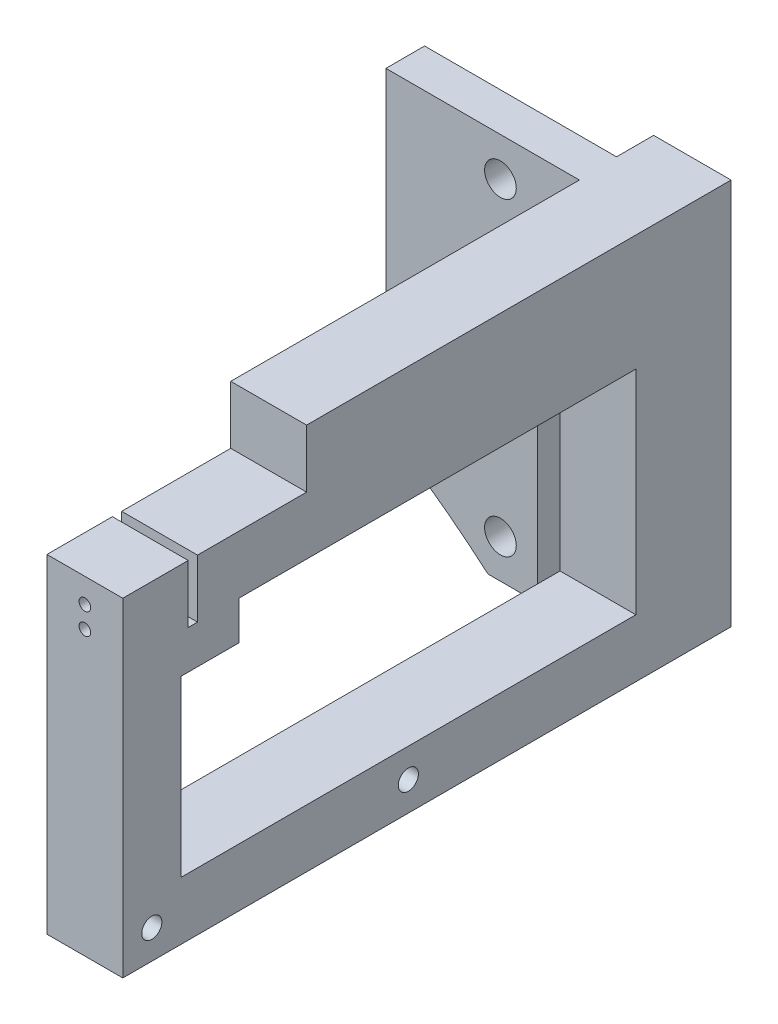
SolidWorks part; units mm, degrees
ref_plane "Front Plane" through (0, 0, 0) normal (0, 0, 1) x (1, 0, 0)
ref_plane "Top Plane" through (0, 0, 0) normal (0, 1, 0) x (1, 0, 0)
ref_plane "Right Plane" through (0, 0, 0) normal (1, 0, 0) x (0, 0, -1)
sketch "Sketch1" plane through (0, 0, 0) normal (0, 0, 1) x (1, 0, 0)
  line L0 (95.25, -31.75) -> (86.8503, -31.75) construction
  line L1 (94.996, -31.75) -> (86.8503, -31.75)
  line L2 (70.104, -19.2524) -> (70.104, -19.41)
  line L32 (70.104, 22.225) -> (70.104, 31.75)
  line L33 (70.104, -19.2524) -> (70.104, 22.225)
  line L34 (70.104, -19.2524) -> (70.104, 22.225)
  line L35 (101.6, 31.75) -> (3.175, 31.75) construction
  line L36 (101.6, 22.479) -> (101.6, 31.75)
  line L54 (70.104, 31.75) -> (101.6, 31.75)
  line L58 (94.996, 22.479) -> (101.6, 22.479)
  line L59 (94.996, -31.75) -> (94.996, 22.479)
  line L60 (94.996, 22.479) -> (101.6, 22.479)
  line L61 (94.996, -31.75) -> (94.996, 22.479)
  circle A0 centre (88.9, -25.4) radius 2.6 construction
  circle A1 centre (88.9, -25.4) radius 2.6
  circle A6 centre (88.9, 25.4) radius 2.6 construction
  circle A7 centre (88.9, 25.4) radius 2.6
  arc A8 (86.8503, -31.75) -> (69.85, -19.2524) centre (0, -132.08) ccw construction
  arc A9 (86.8503, -31.75) -> (70.104, -19.41) centre (0, -132.08) ccw
  dimension "D2" = 0.254
  dimension "D3" = 0.254
extrude "Boss-Extrude1" add sketch "Sketch1" along normal blind 6.35
sketch "Sketch2" plane through (0, 0, 6.35) normal (0, 0, 1) x (1, 0, 0)
  line L0 (101.6, 22.479) -> (101.854, 22.479)
  line L1 (94.996, 22.479) -> (101.6, 22.479) construction
  line L2 (101.854, 22.479) -> (101.854, -31.75)
  line L3 (101.854, -31.75) -> (114.3, -31.75)
  line L4 (114.3, -31.75) -> (114.3, 31.75)
  line L5 (114.3, 31.75) -> (101.6, 31.75)
  line L6 (101.6, 22.479) -> (101.6, 31.75) construction
  line L7 (101.6, 31.75) -> (101.6, 22.479)
  point P7 (0, 0)
  dimension "D1" = 12.7
  dimension "D2" = 0.254
extrude "Boss-Extrude2" add sketch "Sketch2" against normal offset from surface (12.446 mm away) 0.254
sketch "Sketch3" plane through (114.3, 0, 0) normal (1, 0, 0) x (0, 0, -1)
  line L0 (-6.35, -31.75) -> (-6.35, 22.225)
  line L1 (-93.725, -31.75) -> (-93.725, 22.225)
  line L2 (-93.725, 22.225) -> (-87.375, 22.225)
  line L4 (6.35, -31.75) -> (-93.725, -31.75) construction
  line L5 (-87.375, 22.225) -> (0, 22.225) construction
  line L6 (-84.2, 12.7) -> (-84.2, -22.225) construction
  line L7 (-84.2, -22.225) -> (-9.525, -22.225) construction
  line L8 (-9.525, 12.7) -> (-84.2, 12.7) construction
  line L9 (-9.525, -22.225) -> (-9.525, 12.7) construction
  line L10 (-6.35, -31.75) -> (-93.725, -31.75)
  line L11 (-87.375, 22.225) -> (-6.35, 22.225)
  line L12 (-84.2, 12.7) -> (-84.2, -22.225)
  line L13 (-84.2, -22.225) -> (-9.525, -22.225)
  line L14 (-9.525, 12.7) -> (-84.2, 12.7)
  line L15 (-9.525, -22.225) -> (-9.525, 12.7)
  line L16 (-87.375, 22.225) -> (0, 22.225) construction
  line L17 (-6.35, -31.75) -> (-6.35, 31.75) construction
  line L18 (-84.2, -4.7625) -> (-9.525, -4.7625)
extrude "Boss-Extrude4" add sketch "Sketch3" against normal offset from surface (12.446 mm away) 0.254 contours L11 L2 L1 L10 L8 L15 L13 L12 L14 region at (114.3, -30.723, 50.0375)
sketch "Sketch6" plane through (0, 22.225, 0) normal (0, 1, 0) x (1, 0, 0)
  line L1 (101.854, -6.35) -> (114.3, -6.35)
  line L2 (101.854, -6.35) -> (101.854, -63.5625)
  line L3 (101.854, -63.5625) -> (114.3, -63.5625)
  line L4 (114.3, -6.35) -> (114.3, -63.5625)
  line L5 (114.3, -93.725) -> (114.3, -6.35) construction
  line L6 (57.15, -65.15) -> (-95.25, -65.15) construction
  point P5 (107.95, -58.3606)
  dimension "D1" = 1.5875
extrude "Boss-Extrude5" add sketch "Sketch6" along normal up to surface (9.525 mm away) up to face at (95.3347, 31.75, 0.0847)
sketch "Sketch7" plane through (114.3, 0, 0) normal (1, 0, 0) x (0, 0, -1)
  line L1 (-84.2, -22.225) -> (-9.525, -22.225) construction
  line L2 (-93.725, -31.75) -> (-93.725, 22.225) construction
  line L3 (-155.075, -31.75) -> (-45.075, -31.75) construction
  circle A0 centre (-88.9625, -26.9875) radius 1.65
  circle A1 centre (-46.8625, -26.9875) radius 1.65
  point P4 (0, 0)
  point P5 (-50.3003, -43.0881)
  point P8 (0, 0)
  point P9 (-49.9562, -28.12)
  point P10 (-46.8625, -22.225)
  point P11 (0, 0)
  point P12 (0, 0)
  point P17 (0, 0)
  dimension "D3" = 3.3
  dimension "D1" = 4.7625
  dimension "D2" = 4.7625
extrude "Cut-Extrude2" cut sketch "Sketch7" against normal through all both
sketch "Sketch8" plane through (114.3, 0, 0) normal (1, 0, 0) x (0, 0, -1)
  line L0 (6.096, -31.75) -> (6.096, 31.75) construction
  line L1 (6.096, 31.75) -> (-63.5625, 31.75) construction
  line L2 (-63.5625, 31.75) -> (-63.5625, 22.225) construction
  line L3 (-93.725, 22.225) -> (-63.5625, 22.225) construction
  line L4 (6.096, 12.7) -> (6.096, 31.75)
  line L5 (6.096, 31.75) -> (-63.5625, 31.75)
  line L6 (-63.5625, 31.75) -> (-63.5625, 22.225)
  line L7 (-93.725, 22.225) -> (-63.5625, 22.225)
  line L8 (-9.525, 12.7) -> (-84.2, 12.7) construction
  line L9 (-93.725, -31.75) -> (-93.725, 22.225) construction
  line L10 (-9.525, 12.7) -> (-84.2, 12.7)
  line L11 (-93.725, 12.7) -> (-93.725, 22.225)
  line L12 (-84.2, 12.7) -> (-93.725, 12.7)
  line L13 (-9.525, 12.7) -> (6.096, 12.7)
  line L15 (-93.725, 12.7) -> (-74.675, 12.7)
  line L16 (-93.725, 12.7) -> (-93.725, 6.35)
  line L17 (-93.725, 6.35) -> (-74.675, 6.35)
  line L18 (-74.675, 12.7) -> (-74.675, 6.35)
  line M3 (6.096, 31.75) -> (-63.5625, 31.75)
  line M4 (-63.5625, 31.75) -> (-63.5625, 22.225)
  line M5 (-63.5625, 22.225) -> (-93.725, 22.225)
  line M6 (-93.725, 22.225) -> (-93.725, -31.75)
  line M8 (6.096, -31.75) -> (6.096, 31.75)
  line M11 (-84.2, -22.225) -> (-84.2, 12.7)
  line M12 (-84.2, 12.7) -> (-9.525, 12.7)
  dimension "D1" = 19.05
  dimension "D2" = 6.35
extrude "Boss-Extrude6" add sketch "Sketch8" against normal up to surface (12.446 mm away) contours L10 L13 L12 M12 M8 M3 M4 M5 M6 | L17 L12 M6 M11 | L18 L17 M12 M11 | L16 L15 L18 L17 region at (114.3, 21.3774, 37.6159) region at (114.3, 9.525, 79.4375) region at (114.3, 9.525, 88.9625) up to face at (101.854, -26.9875, 90.6125)
sketch "Sketch9" plane through (101.854, 0, 0) normal (-1, 0, 0) x (0, 0, 1)
  line L0 (82.225, 22.225) -> (82.225, 12.7)
  line L4 (93.725, -31.75) -> (93.725, 22.225) construction
  line L5 (93.725, 22.225) -> (63.5625, 22.225) construction
  point P4 (0, 0)
  dimension "D1" = 9.525
  dimension "D2" = 11.5
extrude "Cut-Extrude-Thin1" cut sketch "Sketch9" against normal through all both and the other way through all thin thin type mid plane wall 1.524
sketch "Sketch10" plane through (0, 0, 93.725) normal (0, 0, 1) x (1, 0, 0)
  line L0 (101.854, 22.225) -> (114.3, 22.225) construction
  line L1 (114.3, 12.7) -> (101.854, 12.7) construction
  line L2 (114.3, 22.225) -> (101.854, 22.225) construction
  circle A1 centre (108.077, 14.7) radius 0.95
  circle A2 centre (108.077, 18.225) radius 0.95
  point P4 (0, 0)
  point P7 (108.077, 22.225)
  dimension "D1" = 1.9
  dimension "D2" = 2
  dimension "D3" = 4
extrude "Cut-Extrude3" cut sketch "Sketch10" against normal up to surface (12.262 mm away) up to face at (108.077, 17.4625, 81.463)
equation "\"D3@Sketch7\"=3.3mm"
equation "\"D1@Sketch10\"=1.9mm"
equation "\"D3@Sketch10\"=4mm"
equation "\"D2@Sketch10\"=2mm"
